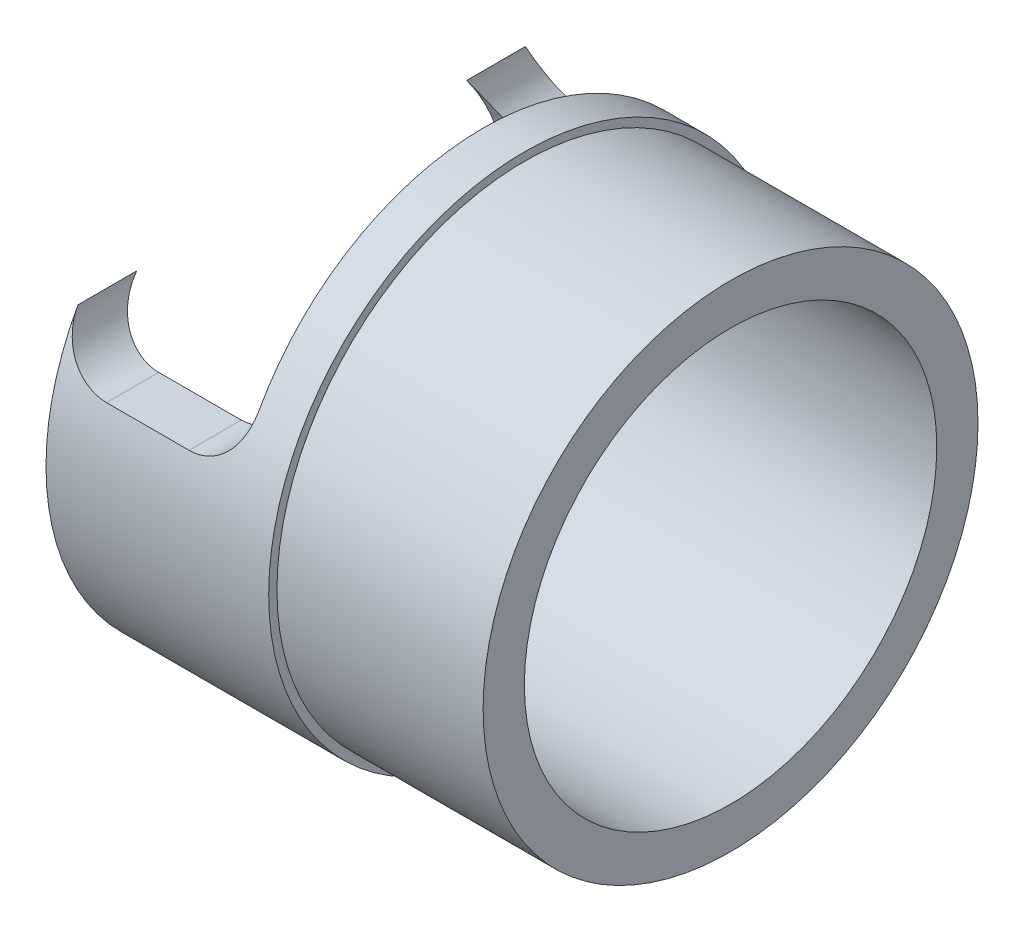
SolidWorks part; units mm, degrees
ref_plane "Front Plane" through (0, 0, 0) normal (0, 0, 1) x (1, 0, 0)
ref_plane "Top Plane" through (0, 0, 0) normal (0, 1, 0) x (1, 0, 0)
ref_plane "Right Plane" through (0, 0, 0) normal (1, 0, 0) x (0, 0, -1)
sketch "Sketch1" plane through (0, 0, 0) normal (0, 0, 1) x (1, 0, 0)
  line L0 (-49, 0) -> (49, 0) construction
  line L1 (49, 0) -> (49, 25) construction
  line L2 (49, 25) -> (19, 25)
  line L3 (19, 25) -> (19, 31)
  line L4 (19, 31) -> (24, 31)
  line L5 (24, 31) -> (24, 30)
  line L6 (24, 30) -> (49, 30)
  line L7 (49, 30) -> (49, 25)
revolve "Revolve1" add sketch "Sketch1" angle 360 about L0
sketch "Sketch3" plane through (19, 0, 0) normal (-1, 0, 0) x (0, 0, 1)
  circle A1 centre (0, 0) radius 31
  circle A2 centre (0, 0) radius 31
  circle A3 centre (0, 0) radius 25
  circle A4 centre (0, 0) radius 31
  circle M2 centre (0, 0) radius 25
  circle M3 centre (0, 0) radius 31
  dimension "D1" = 0
extrude "Boss-Extrude1" add sketch "Sketch3" along normal blind 22 contours M3 M2 region at (19, 0, -30.1232)
sketch "Sketch4" plane through (0, 0, 0) normal (0, 0, 1) x (1, 0, 0)
  line L0 (-3, 31) -> (19, 31)
  line L1 (24, 31) -> (-3, 31) construction
  line L2 (-3, 31) -> (-3, 15)
  line L3 (-3, 31) -> (-3, -31) construction
  line L4 (3, 9) -> (13, 9)
  line L5 (19, 15) -> (19, 31)
  arc A0 (13, 9) -> (19, 15) centre (13, 15) ccw
  arc A1 (3, 9) -> (-3, 15) centre (3, 15) cw
  point P13 (-3, 9)
  dimension "D1" = 6
extrude "Cut-Extrude1" cut sketch "Sketch4" against normal through all both and the other way through all
